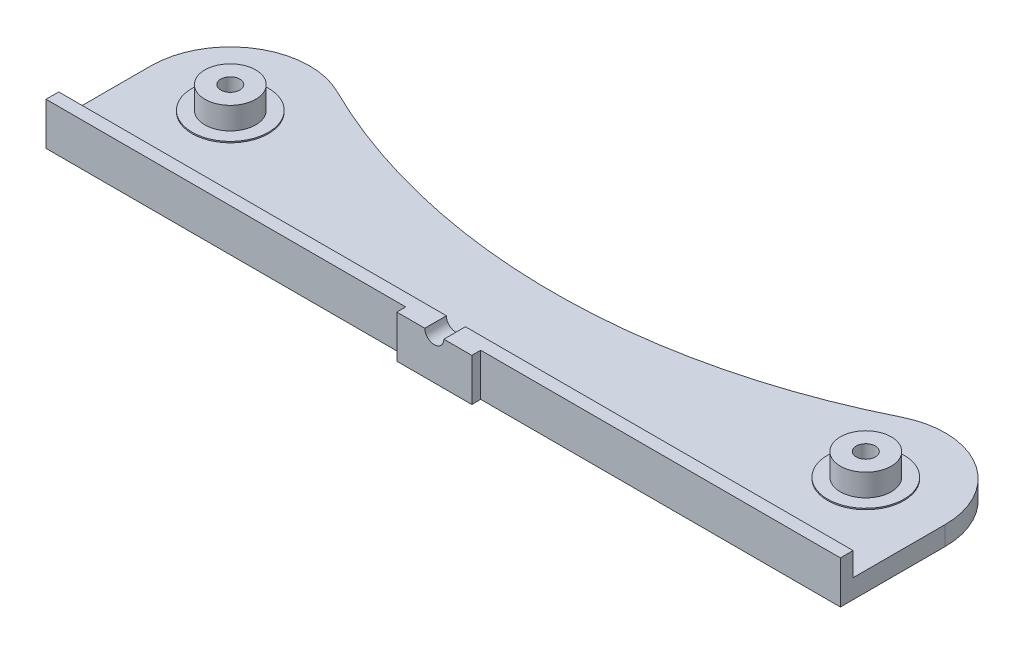
SolidWorks part; units mm, degrees
ref_plane "Front Plane" through (0, 0, 0) normal (0, 0, 1) x (1, 0, 0)
ref_plane "Top Plane" through (0, 0, 0) normal (0, 1, 0) x (1, 0, 0)
ref_plane "Right Plane" through (0, 0, 0) normal (1, 0, 0) x (0, 0, -1)
sketch "Sketch1" plane through (0, 0, 0) normal (0, 1, 0) x (1, 0, 0)
  line L0 (-62.5, 0) -> (62.5, 0)
  line L1 (62.5, 0) -> (62.5, 16.5)
  line L2 (-62.5, 0) -> (-62.5, 16.5)
  line L3 (-62.5, 16.5) -> (62.5, 16.5) construction
  line L4 (-50, 29) -> (50, 29) construction
  line L5 (-5.9, 0) -> (5.9, 0)
  line L6 (-5.9, 0) -> (-5.9, -1.4)
  line L7 (-5.9, -1.4) -> (5.9, -1.4)
  line L8 (5.9, 0) -> (5.9, -1.4)
  line L9 (-62.5, 0) -> (62.5, 0)
  line L10 (-62.5, 0) -> (-62.5, 2)
  line L11 (-62.5, 2) -> (62.5, 2)
  line L12 (62.5, 0) -> (62.5, 2)
  circle A0 centre (-50, 16.5) radius 4
  circle A1 centre (50, 16.5) radius 4
  circle A2 centre (-50, 16.5) radius 12.5
  circle A3 centre (50, 16.5) radius 12.5
  circle A4 centre (0, 117.2782) radius 100
  circle A5 centre (-50, 16.5) radius 1.5
  circle A6 centre (50, 16.5) radius 1.5
  dimension "D4" = 8
  dimension "D5" = 8
  dimension "D6" = 100
  dimension "D7" = 12.5
  dimension "D8" = 3
  dimension "D9" = 3
  dimension "D14" = 200
  dimension "D1" = 125
  dimension "D2" = 62.5
  dimension "D3" = 16.5
  dimension "D10" = 5.9
  dimension "D11" = 11.8
  dimension "D12" = 1.4
  dimension "D13" = 2
extrude "Boss-Extrude1" add sketch "Sketch1" along normal blind 3 contours L3 A2 L2 L0 L1 A3 | A2 L3 A0 | L3 A2 A0 | A0 L3 A5 | L3 A0 A5 | L3 A3 A1 | L3 A1 A6 | A3 L3 A1 | A1 L3 A6 | L3 A3 | A2 L3 | L6 L5 L8 L7 | L10 L9 L12 L11 region at (0, 0, -10.2839) region at (-56.4017, 0, -26.8225) region at (43.5983, 0, -6.1775) region at (-53.8869, 0, -16.5) region at (46.1131, 0, -16.5)
extrude "Boss-Extrude2" add sketch "Sketch1<3>" along normal blind 3.7 from surface contours L3 A0 A5 | A0 L3 A5 | A1 L3 A6 | L3 A1 A6 | L8 L0 L6 L7 | L10 L9 L12 L11 region at (0, 0, 0.7) region at (-53.8869, 0, -16.5) region at (46.1131, 0, -16.5) starting at face at (0, 3, -8.5224)
sketch "Sketch1<3>" plane through (0, 0, 0) normal (0, 1, 0) x (1, 0, 0) same geometry as "Sketch1"
sketch "Sketch2" plane through (0, 0, -2) normal (0, 0, -1) x (-1, 0, 0)
  line L0 (-62.5, 6.7) -> (62.5, 6.7) construction
  circle A0 centre (0, 6.7) radius 1.5
  dimension "D2" = 3
  dimension "D1" = 0
extrude "Cut-Extrude1" cut sketch "Sketch2" against normal through all
sketch "Sketch3" plane through (0, 3, 0) normal (0, 1, 0) x (1, 0, 0)
  circle A0 centre (-50, 16.5) radius 6
  circle A1 centre (-50, 16.5) radius 1.5
  circle A2 centre (50, 16.5) radius 1.5
  circle A3 centre (50, 16.5) radius 6
  dimension "D1" = 3
  dimension "D2" = 12
  dimension "D3" = 12
  dimension "D4" = 3
extrude "Boss-Extrude3" add sketch "Sketch3" along normal blind 0.2
